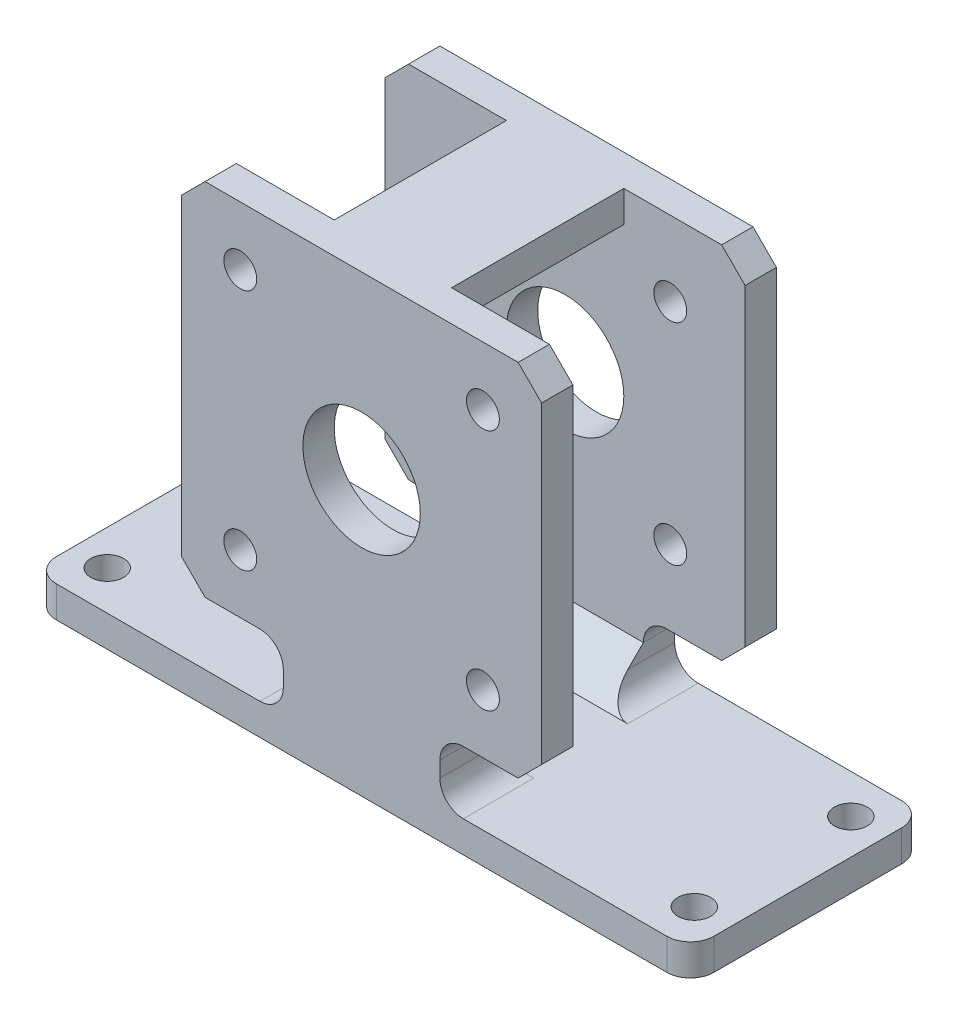
SolidWorks part; units mm, degrees
material "7050-T73510"
ref_plane "前视基准面" through (0, 0, 0) normal (0, 0, 1) x (1, 0, 0)
ref_plane "上视基准面" through (0, 0, 0) normal (0, 1, 0) x (1, 0, 0)
ref_plane "右视基准面" through (0, 0, 0) normal (1, 0, 0) x (0, 0, -1)
sketch "草图1" plane through (0, 0, 0) normal (0, 0, 1) x (1, 0, 0)
  circle A0 centre (0, 0) radius 23
  dimension "D1" = 46
extrude "凸台-拉伸1" add sketch "草图1" along normal blind 4
sketch "草图2" plane through (0, 0, 4) normal (0, 0, 1) x (1, 0, 0)
  circle A0 centre (0, 0) radius 7.5
  dimension "D1" = 15
extrude "切除-拉伸1" cut sketch "草图2" against normal blind 4
ref_plane "基准面1" through (0, 0, 24) normal (0, 0, 1) x (1, 0, 0)
sketch "草图3" plane through (0, 0, 24) normal (0, 0, 1) x (1, 0, 0)
  line L1 (-23, -23) -> (23, -23)
  line L2 (-23, -23) -> (-23, 23)
  line L3 (-23, 23) -> (23, 23)
  line L4 (23, -23) -> (23, 23)
  line L5 (-23, -23) -> (23, 23) construction
  line L6 (-23, 23) -> (23, -23) construction
  point P0 (0, 0)
  dimension "D1" = 46
  dimension "D2" = 46
extrude "凸台-拉伸2" add sketch "草图3" along normal blind 4 separate body
sketch "草图4" plane through (0, 0, 24) normal (0, 0, -1) x (-1, 0, 0)
  circle A0 centre (0, 0) radius 7.5
  dimension "D1" = 15
extrude "切除-拉伸2" cut sketch "草图4" against normal blind 4
sketch "草图5" plane through (0, 0, 28) normal (0, 0, 1) x (1, 0, 0)
  line L1 (-15.5, -15.5) -> (15.5, -15.5) construction
  line L2 (-15.5, -15.5) -> (-15.5, 15.5) construction
  line L3 (-15.5, 15.5) -> (15.5, 15.5) construction
  line L4 (15.5, -15.5) -> (15.5, 15.5) construction
  line L5 (-15.5, -15.5) -> (15.5, 15.5) construction
  line L6 (-15.5, 15.5) -> (15.5, -15.5) construction
  circle A0 centre (15.5, 15.5) radius 2.1
  circle A1 centre (15.5, -15.5) radius 2.1
  circle A2 centre (-15.5, -15.5) radius 2.1
  circle A3 centre (-15.5, 15.5) radius 2.1
  point P0 (0, 0)
  dimension "D3" = 4.2
  dimension "D1" = 31
  dimension "D2" = 31
extrude "切除-拉伸3" cut sketch "草图5" against normal blind 4
chamfer "倒角1" distance 3 angle 45 4 edges at (-23, -23, 26) (23, -23, 26) (23, 23, 26) (-23, 23, 26)
sketch "草图6" plane through (0, 0, 0) normal (0, 0, -1) x (-1, 0, 0)
  line L0 (0, 0) -> (0, 19) construction
  line L1 (0, 0) -> (13.435, 13.435) construction
  circle A0 centre (0, 0) radius 19 construction
  circle A1 centre (13.435, 13.435) radius 2.1
  dimension "D1" = 38
  dimension "D3" = 4.2
  dimension "D2" = 45
extrude "切除-拉伸4" cut sketch "草图6" against normal blind 4
pattern_circular "阵列(圆周)1" count 4 over 360 about axis through (0, 0, 0) along (0, 0, 1) of "切除-拉伸4"
sketch "草图7" plane through (0, 0, 0) normal (0, 0, -1) x (-1, 0, 0)
  line L8 (-20, -23) -> (20, -23)
  line L9 (20, -23) -> (23, -20)
  line L10 (23, -20) -> (23, 20)
  line L11 (23, 20) -> (20, 23)
  line L12 (20, 23) -> (-20, 23)
  line L13 (-20, 23) -> (-23, 20)
  line L14 (-23, 20) -> (-23, -20)
  line L15 (-23, -20) -> (-20, -23)
  line L16 (-20, -23) -> (20, -23)
  line L17 (20, -23) -> (23, -20)
  line L18 (23, -20) -> (23, 20)
  line L19 (23, 20) -> (20, 23)
  line L20 (20, 23) -> (-20, 23)
  line L21 (-20, 23) -> (-23, 20)
  line L22 (-23, 20) -> (-23, -20)
  line L23 (-23, -20) -> (-20, -23)
  circle A1 centre (0, 0) radius 23
  circle A2 centre (0, 0) radius 23
  circle M15 centre (0, 0) radius 23
  dimension "D1" = 0
  dimension "D2" = 0
extrude "凸台-拉伸3" add sketch "草图7" against normal up to surface (4 mm away) contours L21 L22 L20 M15 | L19 L20 L18 M15 | L17 L18 L16 M15 | L22 L23 L16 M15 region at (17.6918, -17.6918, 0) region at (-17.6918, -17.6918, 0) region at (17.6918, 17.6918, 0) region at (-17.6918, 17.6918, 0) up to face at (-13.435, -15.535, 4)
ref_plane "基准面3" through (0, 0, 14) normal (0, 0, -1) x (-1, 0, 0)
sketch "草图16" plane through (0, 0, 14) normal (0, 0, -1) x (-1, 0, 0)
  line L1 (-42, -35) -> (42, -35)
  line L2 (-42, -35) -> (-42, -31)
  line L3 (-42, -31) -> (42, -31)
  line L4 (42, -35) -> (42, -31)
  line L5 (-42, -35) -> (42, -31) construction
  line L6 (-42, -31) -> (42, -35) construction
  point P0 (0, -33)
  dimension "D1" = 35
  dimension "D2" = 4
  dimension "D3" = 84
extrude "凸台-拉伸11" add sketch "草图16" along normal mid plane 30 separate body
sketch "草图17" plane through (0, 0, 0) normal (0, 0, -1) x (-1, 0, 0)
  line L0 (-20, -23) -> (20, -23) construction
  line L1 (-10, -31) -> (10, -31)
  line L2 (-10, -31) -> (-10, -23)
  line L3 (-10, -23) -> (10, -23)
  line L4 (10, -31) -> (10, -23)
  line L5 (-10, -31) -> (10, -23) construction
  line L6 (-10, -23) -> (10, -31) construction
  line L7 (42, -31) -> (-42, -31) construction
  point P0 (0, -27)
  dimension "D1" = 20
extrude "凸台-拉伸13" add sketch "草图17" against normal up to surface (4 mm away) contours L4 L3 L2 L1 up to face at (-13.435, -15.535, 4)
sketch "草图18" plane through (0, 0, 28) normal (0, 0, 1) x (1, 0, 0)
  line L4 (-10, -31) -> (10, -31)
  line L5 (-10, -23) -> (-10, -31)
  line L6 (10, -23) -> (-10, -23)
  line L7 (10, -31) -> (10, -23)
  line L8 (-10, -31) -> (10, -31)
  line L9 (-10, -23) -> (-10, -31)
  line L10 (10, -23) -> (-10, -23)
  line L11 (10, -31) -> (10, -23)
  dimension "D1" = 0
extrude "凸台-拉伸14" add sketch "草图18" against normal up to surface (4 mm away) up to face at (-13.4, 15.5, 24)
fillet "圆角1" radius 3 4 edges at (-42, -33, -1) (-42, -33, 29) (42, -33, 29) (42, -33, -1)
sketch "草图20" plane through (0, -31, 0) normal (0, 1, 0) x (1, 0, 0)
  line L1 (-37.5, -24) -> (37.5, -24) construction
  line L2 (-37.5, -24) -> (-37.5, -4) construction
  line L3 (-37.5, -4) -> (37.5, -4) construction
  line L4 (37.5, -24) -> (37.5, -4) construction
  line L5 (-37.5, -24) -> (37.5, -4) construction
  line L6 (-37.5, -4) -> (37.5, -24) construction
  circle A0 centre (-37.5, -4) radius 2.1
  circle A1 centre (37.5, -4) radius 2.1
  circle A2 centre (37.5, -24) radius 2.1
  circle A3 centre (-37.5, -24) radius 2.1
  point P0 (0, -14)
  dimension "D4" = 4.2
  dimension "D1" = 14
  dimension "D2" = 20
  dimension "D3" = 75
extrude "切除-拉伸6" cut sketch "草图20" against normal blind 30
fillet "圆角2" radius 3 10 edges at (0, -31, 24) (0, -31, 4) (10, -31, 2) (10, -31, 26) (-10, -31, 2) (-10, -31, 26) (-10, -23, 26) (10, -23, 26) (10, -23, 2) (-10, -23, 2)
sketch "草图22" plane through (0, 0, 28) normal (0, 0, 1) x (1, 0, 0)
  line L0 (20, 23) -> (-20, 23) construction
  line L1 (-7.5, 19) -> (7.5, 19)
  line L2 (-7.5, 19) -> (-7.5, 23)
  line L3 (-7.5, 23) -> (7.5, 23)
  line L4 (7.5, 19) -> (7.5, 23)
  line L5 (-7.5, 19) -> (7.5, 23) construction
  line L6 (-7.5, 23) -> (7.5, 19) construction
  point P0 (0, 21)
  dimension "D1" = 15
  dimension "D2" = 4
extrude "凸台-拉伸16" add sketch "草图22" against normal up to surface (24 mm away) up to face at (-13.435, -15.535, 4)
sketch "草图23" plane through (0, 0, 28) normal (0, 0, 1) x (1, 0, 0)
  line L12 (20, 23) -> (-20, 23)
  line L13 (-20, 23) -> (-23, 20)
  line L14 (-23, 20) -> (-23, -20)
  line L15 (-23, -20) -> (-20, -23)
  line L16 (-20, -23) -> (-13, -23)
  line L17 (-10, -26) -> (-10, -28)
  line L18 (-13, -31) -> (13, -31)
  line L19 (10, -28) -> (10, -26)
  line L20 (13, -23) -> (20, -23)
  line L21 (20, -23) -> (23, -20)
  line L22 (23, -20) -> (23, 20)
  line L23 (23, 20) -> (20, 23)
  line L24 (20, 23) -> (-20, 23)
  line L25 (-20, 23) -> (-23, 20)
  line L26 (-23, 20) -> (-23, -20)
  line L27 (-23, -20) -> (-20, -23)
  line L28 (-20, -23) -> (-13, -23)
  line L29 (-10, -26) -> (-10, -28)
  line L30 (-13, -31) -> (13, -31)
  line L31 (10, -28) -> (10, -26)
  line L32 (13, -23) -> (20, -23)
  line L33 (20, -23) -> (23, -20)
  line L34 (23, -20) -> (23, 20)
  line L35 (23, 20) -> (20, 23)
  circle A0 centre (15.5, 15.5) radius 2.1 construction
  circle A1 centre (15.5, -15.5) radius 2.1 construction
  circle A2 centre (0, 0) radius 7.5 construction
  circle A3 centre (-15.5, 15.5) radius 2.1 construction
  arc A4 (-10, -26) -> (-13, -23) centre (-13, -26) ccw
  arc A5 (-13, -31) -> (-10, -28) centre (-13, -28) ccw
  arc A6 (10, -28) -> (13, -31) centre (13, -28) ccw
  arc A7 (13, -23) -> (10, -26) centre (13, -26) ccw
  arc A8 (-10, -26) -> (-13, -23) centre (-13, -26) ccw
  arc A9 (-13, -31) -> (-10, -28) centre (-13, -28) ccw
  arc A10 (10, -28) -> (13, -31) centre (13, -28) ccw
  arc A11 (13, -23) -> (10, -26) centre (13, -26) ccw
  circle A12 centre (-15.5, -15.5) radius 2.1 construction
  circle A13 centre (15.5, 15.5) radius 2.1
  circle A14 centre (15.5, -15.5) radius 2.1
  circle A15 centre (0, 0) radius 7.5
  circle A16 centre (-15.5, 15.5) radius 2.1
  circle A17 centre (-15.5, -15.5) radius 2.1
  dimension "D1" = 0
extrude "凸台-拉伸17" add sketch "草图23" along normal up to surface (1 mm away) up to face at (0, -33, 29)
sketch "草图24" plane through (0, 0, 0) normal (0, 0, -1) x (-1, 0, 0)
  line L12 (-23, 20) -> (-23, -20)
  line L13 (-23, -20) -> (-20, -23)
  line L14 (-20, -23) -> (-13, -23)
  line L15 (-10, -26) -> (-10, -28)
  line L16 (-13, -31) -> (13, -31)
  line L17 (10, -28) -> (10, -26)
  line L18 (13, -23) -> (20, -23)
  line L19 (20, -23) -> (23, -20)
  line L20 (23, -20) -> (23, 20)
  line L21 (23, 20) -> (20, 23)
  line L22 (20, 23) -> (-20, 23)
  line L23 (-20, 23) -> (-23, 20)
  line L24 (-23, 20) -> (-23, -20)
  line L25 (-23, -20) -> (-20, -23)
  line L26 (-20, -23) -> (-13, -23)
  line L27 (-10, -26) -> (-10, -28)
  line L28 (-13, -31) -> (13, -31)
  line L29 (10, -28) -> (10, -26)
  line L30 (13, -23) -> (20, -23)
  line L31 (20, -23) -> (23, -20)
  line L32 (23, -20) -> (23, 20)
  line L33 (23, 20) -> (20, 23)
  line L34 (20, 23) -> (-20, 23)
  line L35 (-20, 23) -> (-23, 20)
  circle A0 centre (-13.435, -13.435) radius 2.1 construction
  circle A1 centre (13.435, -13.435) radius 2.1 construction
  circle A2 centre (0, 0) radius 7.5 construction
  circle A3 centre (-13.435, 13.435) radius 2.1 construction
  arc A4 (-10, -26) -> (-13, -23) centre (-13, -26) ccw
  arc A5 (-13, -31) -> (-10, -28) centre (-13, -28) ccw
  arc A6 (10, -28) -> (13, -31) centre (13, -28) ccw
  arc A7 (13, -23) -> (10, -26) centre (13, -26) ccw
  arc A8 (-10, -26) -> (-13, -23) centre (-13, -26) ccw
  arc A9 (-13, -31) -> (-10, -28) centre (-13, -28) ccw
  arc A10 (10, -28) -> (13, -31) centre (13, -28) ccw
  arc A11 (13, -23) -> (10, -26) centre (13, -26) ccw
  circle A12 centre (13.435, 13.435) radius 2.1 construction
  circle A13 centre (-13.435, -13.435) radius 2.1
  circle A14 centre (13.435, -13.435) radius 2.1
  circle A15 centre (0, 0) radius 7.5
  circle A16 centre (-13.435, 13.435) radius 2.1
  circle A17 centre (13.435, 13.435) radius 2.1
  dimension "D1" = 0
extrude "凸台-拉伸18" add sketch "草图24" along normal up to surface (1 mm away) up to face at (0, -33, -1)
sketch "草图25" plane through (0, 0, 0) normal (1, 0, 0) x (0, 0, -1)
  line L0 (-4, 19) -> (-24, 19) construction
  line L1 (-25, -31) -> (-3, -31)
  line L2 (-25, -31) -> (-25, 19)
  line L3 (-25, 19) -> (-3, 19)
  line L4 (-3, -31) -> (-3, 19)
  line L5 (-25, -31) -> (-3, 19) construction
  line L6 (-25, 19) -> (-3, -31) construction
  line L7 (-2, -31) -> (-26, -31) construction
  line L8 (1, -20) -> (1, 20) construction
  line L9 (-29, -20) -> (-29, 20) construction
  point P0 (-14, -6)
  dimension "D1" = 4
  dimension "D2" = 4
extrude "切除-拉伸7" cut sketch "草图25" against normal mid plane 500
sketch "草图26" plane through (0, 0, 24) normal (0, 0, -1) x (-1, 0, 0)
  line L5 (-23, 19) -> (-7.5, 19)
  line L6 (-7.5, 19) -> (-7.5, 23)
  line L7 (-7.5, 23) -> (-20, 23)
  line L8 (-20, 23) -> (-23, 20)
  line L9 (-23, 20) -> (-23, 19)
  line L10 (-23, 19) -> (-7.5, 19)
  line L11 (-7.5, 19) -> (-7.5, 23)
  line L12 (-7.5, 23) -> (-20, 23)
  line L13 (-20, 23) -> (-23, 20)
  line L14 (-23, 20) -> (-23, 19)
  dimension "D1" = 0
extrude "切除-拉伸8" cut sketch "草图26" against normal up to surface (1 mm away) up to face at (17.6, 15.5, 25)
mirror "镜向1" about plane through (0, 0, 0) normal (1, 0, 0) of "切除-拉伸8"
sketch "草图27" plane through (0, 0, 4) normal (0, 0, 1) x (1, 0, 0)
  line L5 (-23, 19) -> (-7.5, 19)
  line L6 (-7.5, 19) -> (-7.5, 23)
  line L7 (-7.5, 23) -> (-20, 23)
  line L8 (-20, 23) -> (-23, 20)
  line L9 (-23, 20) -> (-23, 19)
  line L10 (-23, 19) -> (-7.5, 19)
  line L11 (-7.5, 19) -> (-7.5, 23)
  line L12 (-7.5, 23) -> (-20, 23)
  line L13 (-20, 23) -> (-23, 20)
  line L14 (-23, 20) -> (-23, 19)
  line L15 (7.5, 19) -> (23, 19)
  line L16 (23, 19) -> (23, 20)
  line L17 (23, 20) -> (20, 23)
  line L18 (20, 23) -> (7.5, 23)
  line L19 (7.5, 23) -> (7.5, 19)
  line L20 (7.5, 19) -> (23, 19)
  line L21 (23, 19) -> (23, 20)
  line L22 (23, 20) -> (20, 23)
  line L23 (20, 23) -> (7.5, 23)
  line L24 (7.5, 23) -> (7.5, 19)
  dimension "D1" = 0
  dimension "D2" = 0
extrude "切除-拉伸9" cut sketch "草图27" against normal up to surface (1 mm away) up to face at (-15.535, 13.435, 3)
chamfer "倒角2" distance 5 angle 45 2 edges at (0, -31, 3) (0, -31, 25)
